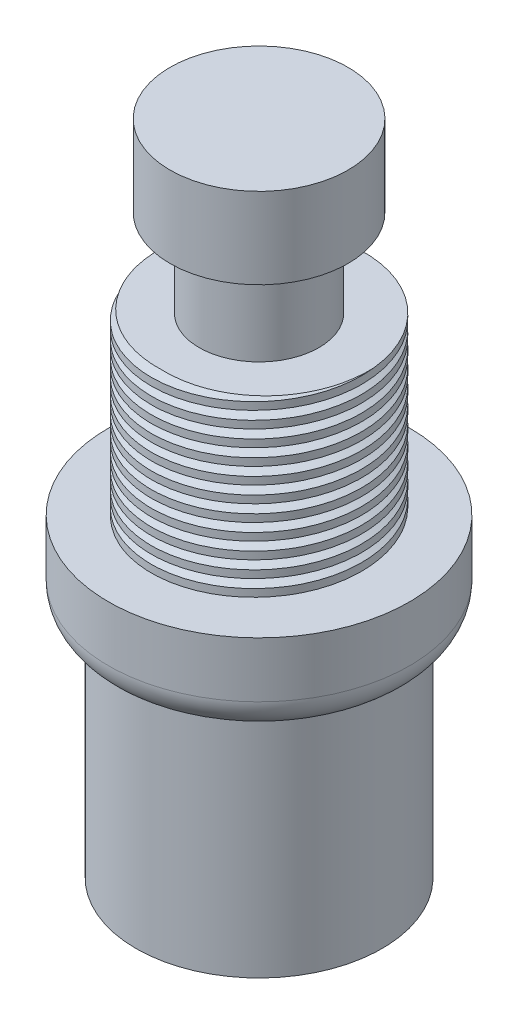
SolidWorks part; units mm, degrees
ref_plane "Front Plane" through (0, 0, 0) normal (0, 0, 1) x (1, 0, 0)
ref_plane "Top Plane" through (0, 0, 0) normal (0, 1, 0) x (1, 0, 0)
ref_plane "Right Plane" through (0, 0, 0) normal (1, 0, 0) x (0, 0, -1)
sketch "Sketch1" plane through (0, 0, 0) normal (0, 1, 0) x (1, 0, 0)
  circle A0 centre (0, 0) radius 3.8
  dimension "D1" = 7.6
extrude "Boss-Extrude1" add sketch "Sketch1" along normal blind 7
sketch "Sketch2" plane through (0, 7, 0) normal (0, 1, 0) x (1, 0, 0)
  circle A0 centre (0, 0) radius 4.65
  dimension "D1" = 9.3
extrude "Boss-Extrude2" add sketch "Sketch2" along normal blind 2.7
sketch "Sketch3" plane through (0, 9.7, 0) normal (0, 1, 0) x (1, 0, 0)
  circle A0 centre (0, 0) radius 3.25
  dimension "D1" = 6.5
extrude "Boss-Extrude3" add sketch "Sketch3" along normal blind 5.4
sketch "Sketch5" plane through (0, 15.1, 0) normal (0, 1, 0) x (1, 0, 0)
  circle A0 centre (0, 0) radius 3.25 construction
  circle A1 centre (0, 0) radius 3.25
curve "Helix/Spiral1" pitch 0.5 height 5.4 radius 3.25 centre (0, 15.1, 0) axis (0, -1, 0) start towards (0, 0, 1)
sketch "Sketch6" plane through (0, 0, 0) normal (1, 0, 0) x (0, 0, -1)
  line L1 (-3.0191, 15.1) -> (-3.3655, 15.3)
  line L2 (-3.3655, 15.3) -> (-3.3655, 14.9)
  line L3 (-3.3655, 14.9) -> (-3.0191, 15.1)
  circle A0 centre (-3.25, 15.1) radius 0.1155 construction
  point P1 (0, 0)
  dimension "D1" = 0.4
sweep "Cut-Sweep1" cut profiles "Sketch6" path "Helix/Spiral1" align with end faces yes
sketch "Sketch7" plane through (0, 15.1, 0) normal (0, 1, 0) x (1, 0, 0)
  circle A0 centre (0, 0) radius 1.85
  dimension "D1" = 3.7
extrude "Boss-Extrude4" add sketch "Sketch7" along normal blind 2.7
sketch "Sketch8" plane through (0, 17.8, 0) normal (0, 1, 0) x (1, 0, 0)
  circle A0 centre (0, 0) radius 2.75
  dimension "D1" = 5.5
extrude "Boss-Extrude5" add sketch "Sketch8" along normal blind 2.5
fillet "Fillet1" radius 1 1 edges at (0, 7, 4.65)
